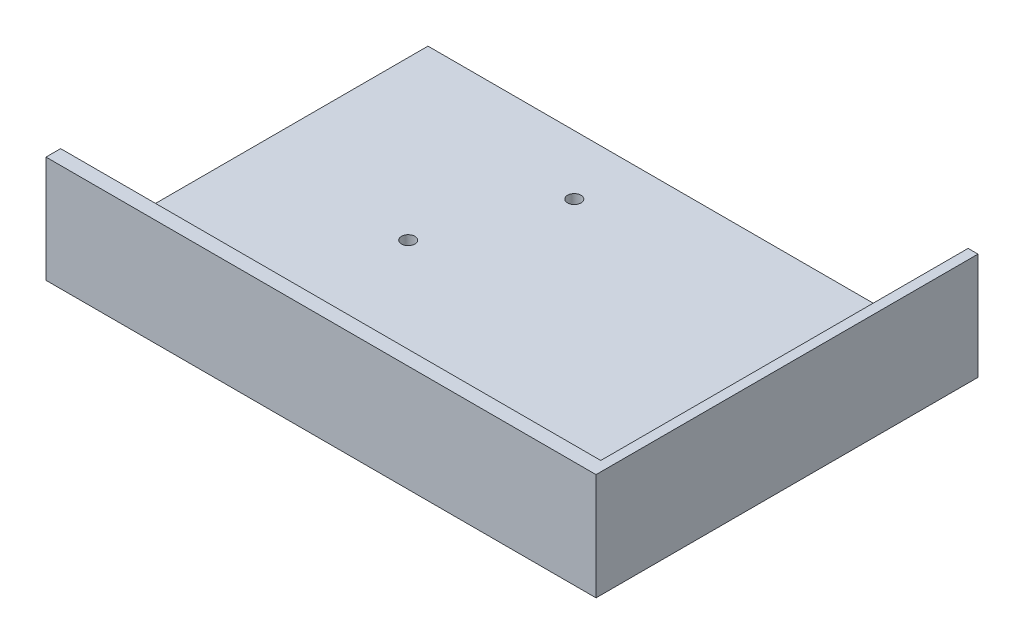
SolidWorks part; units mm, degrees
ref_plane "Front Plane" through (0, 0, 0) normal (0, 0, 1) x (1, 0, 0)
ref_plane "Top Plane" through (0, 0, 0) normal (0, 1, 0) x (1, 0, 0)
ref_plane "Right Plane" through (0, 0, 0) normal (1, 0, 0) x (0, 0, -1)
sketch "Sketch1" plane through (0, 0, 0) normal (0, 1, 0) x (1, 0, 0)
  line L1 (-139.1, -96.6) -> (139.1, -96.6)
  line L2 (-139.1, -96.6) -> (-139.1, 96.6)
  line L3 (-139.1, 96.6) -> (139.1, 96.6)
  line L4 (139.1, -96.6) -> (139.1, 96.6)
  line L5 (-139.1, -96.6) -> (139.1, 96.6) construction
  line L6 (-139.1, 96.6) -> (139.1, -96.6) construction
  dimension "D1" = 278.2
  dimension "D2" = 193.2
extrude "Shell Block" add sketch "Sketch1" along normal blind 27
ref_plane "Shell Front" through (0, 27, 0) normal (0, 1, 0) x (1, 0, 0)
sketch "Sketch2" plane through (0, 27, 0) normal (0, 1, 0) x (1, 0, 0)
  line L1 (-136.6, -92.9) -> (136.6, -92.9)
  line L2 (-136.6, -92.9) -> (-136.6, 92.9)
  line L3 (-136.6, 92.9) -> (136.6, 92.9)
  line L4 (136.6, -92.9) -> (136.6, 92.9)
  line L5 (-136.6, -92.9) -> (136.6, 92.9) construction
  line L6 (-136.6, 92.9) -> (136.6, -92.9) construction
  dimension "D1" = 273.2
  dimension "D2" = 185.8
extrude "Front Opening" cut sketch "Sketch2" against normal blind 1.5
ref_plane "Under Lip" through (0, 25.5, 0) normal (0, 1, 0) x (1, 0, 0)
sketch "Sketch3" plane through (0, 25.5, 0) normal (0, 1, 0) x (1, 0, 0)
  line L1 (-136.6, -94.1) -> (136.6, -94.1)
  line L2 (-136.6, -94.1) -> (-136.6, 94.1)
  line L3 (-136.6, 94.1) -> (136.6, 94.1)
  line L4 (136.6, -94.1) -> (136.6, 94.1)
  line L5 (-136.6, -94.1) -> (136.6, 94.1) construction
  line L6 (-136.6, 94.1) -> (136.6, -94.1) construction
  dimension "D1" = 273.2
  dimension "D2" = 188.2
extrude "Display Pocket" cut sketch "Sketch3" against normal blind 22.5
ref_plane "Back Inner" through (0, 3, 0) normal (0, 1, 0) x (1, 0, 0)
sketch "Sketch4" plane through (0, 3, 0) normal (0, 1, 0) x (1, 0, 0)
  line L1 (-69, 28) -> (-66, 28)
  line L2 (-69, 28) -> (-69, 84)
  line L3 (-69, 84) -> (-66, 84)
  line L4 (-66, 28) -> (-66, 84)
  line L6 (-69, -84) -> (-66, -84)
  line L7 (-69, -84) -> (-69, -28)
  line L8 (-69, -28) -> (-66, -28)
  line L9 (-66, -84) -> (-66, -28)
  line L11 (-77, 28) -> (-74, 28)
  line L12 (-77, 28) -> (-77, 84)
  line L13 (-77, 84) -> (-74, 84)
  line L14 (-74, 28) -> (-74, 84)
  line L16 (-77, -84) -> (-74, -84)
  line L17 (-77, -84) -> (-77, -28)
  line L18 (-77, -28) -> (-74, -28)
  line L19 (-74, -84) -> (-74, -28)
  line L21 (-85, 28) -> (-82, 28)
  line L22 (-85, 28) -> (-85, 84)
  line L23 (-85, 84) -> (-82, 84)
  line L24 (-82, 28) -> (-82, 84)
  line L26 (-85, -84) -> (-82, -84)
  line L27 (-85, -84) -> (-85, -28)
  line L28 (-85, -28) -> (-82, -28)
  line L29 (-82, -84) -> (-82, -28)
  line L31 (-93, 28) -> (-90, 28)
  line L32 (-93, 28) -> (-93, 84)
  line L33 (-93, 84) -> (-90, 84)
  line L34 (-90, 28) -> (-90, 84)
  line L36 (-93, -84) -> (-90, -84)
  line L37 (-93, -84) -> (-93, -28)
  line L38 (-93, -28) -> (-90, -28)
  line L39 (-90, -84) -> (-90, -28)
  line L41 (-101, 28) -> (-98, 28)
  line L42 (-101, 28) -> (-101, 84)
  line L43 (-101, 84) -> (-98, 84)
  line L44 (-98, 28) -> (-98, 84)
  line L46 (-101, -84) -> (-98, -84)
  line L47 (-101, -84) -> (-101, -28)
  line L48 (-101, -28) -> (-98, -28)
  line L49 (-98, -84) -> (-98, -28)
  line L51 (-109, 28) -> (-106, 28)
  line L52 (-109, 28) -> (-109, 84)
  line L53 (-109, 84) -> (-106, 84)
  line L54 (-106, 28) -> (-106, 84)
  line L56 (-109, -84) -> (-106, -84)
  line L57 (-109, -84) -> (-109, -28)
  line L58 (-109, -28) -> (-106, -28)
  line L59 (-106, -84) -> (-106, -28)
  line L61 (-117, 28) -> (-114, 28)
  line L62 (-117, 28) -> (-117, 84)
  line L63 (-117, 84) -> (-114, 84)
  line L64 (-114, 28) -> (-114, 84)
  line L66 (-117, -84) -> (-114, -84)
  line L67 (-117, -84) -> (-117, -28)
  line L68 (-117, -28) -> (-114, -28)
  line L69 (-114, -84) -> (-114, -28)
  line L71 (-125, 28) -> (-122, 28)
  line L72 (-125, 28) -> (-125, 84)
  line L73 (-125, 84) -> (-122, 84)
  line L74 (-122, 28) -> (-122, 84)
  line L76 (-125, -84) -> (-122, -84)
  line L77 (-125, -84) -> (-125, -28)
  line L78 (-125, -28) -> (-122, -28)
  line L79 (-122, -84) -> (-122, -28)
extrude "Vent Slots" cut sketch "Sketch4" against normal blind 4
sketch "Sketch5" plane through (0, 0, 0) normal (1, 0, 0) x (0, 0, -1)
  line L1 (-29, 5) -> (29, 5)
  line L2 (-29, 5) -> (-29, 21)
  line L3 (-29, 21) -> (29, 21)
  line L4 (29, 5) -> (29, 21)
extrude "Cable Exit (-X short side)" cut sketch "Sketch5" against normal blind 140.1
sketch "Sketch6" plane through (0, 3, 0) normal (0, 1, 0) x (1, 0, 0)
  circle A0 centre (-40, -45) radius 1.7
  circle A1 centre (-40, 45) radius 1.7
  circle A2 centre (40, -45) radius 1.7
  circle A3 centre (40, 45) radius 1.7
  circle A4 centre (-52, -15) radius 1.7
  circle A5 centre (-52, 15) radius 1.7
  circle A6 centre (52, -15) radius 1.7
  circle A7 centre (52, 15) radius 1.7
  circle A8 centre (-12, -82) radius 1.7
  circle A9 centre (-12, 82) radius 1.7
  circle A10 centre (12, -82) radius 1.7
  circle A11 centre (12, 82) radius 1.7
  circle A12 centre (-124, -12) radius 1.7
  circle A13 centre (-124, 12) radius 1.7
  circle A14 centre (124, -12) radius 1.7
  circle A15 centre (124, 12) radius 1.7
  circle A16 centre (-72, 12) radius 1.7
  circle A17 centre (-72, -12) radius 1.7
extrude "Bolt Holes" cut sketch "Sketch6" against normal blind 4
sketch "Sketch7" plane through (0, 0, 0) normal (0, 1, 0) x (1, 0, 0)
  line L1 (-200, -200) -> (0, -200)
  line L2 (-200, -200) -> (-200, 200)
  line L3 (-200, 200) -> (0, 200)
  line L4 (0, -200) -> (0, 200)
extrude "Keep one half (X)" cut sketch "Sketch7" against normal through all and the other way through all
sketch "Sketch8" plane through (0, 0, 0) normal (0, 1, 0) x (1, 0, 0)
  line L1 (-200, 0) -> (200, 0)
  line L2 (-200, 0) -> (-200, 200)
  line L3 (-200, 200) -> (200, 200)
  line L4 (200, 0) -> (200, 200)
extrude "Keep one quarter (Z)" cut sketch "Sketch8" against normal through all and the other way through all
equation "\"DispL\"= 272.0"
equation "\"DispW\"= 187.0"
equation "\"DispT\"= 20.0"
equation "\"Clr\"= 0.6"
equation "\"Wall\"= 2.5"
equation "\"BackT\"= 3.0"
equation "\"CableRoom\"= 4.0"
equation "\"LipW\"= 1.2"
equation "\"LipT\"= 1.5"
equation "\"CableW\"= 58.0"
equation "\"CableH\"= 16.0"
equation "\"BoltD\"= 3.4"
equation "\"ShellL\"= \"DispL\" + 2 * \"Clr\" + 2 * \"Wall\""
equation "\"ShellW\"= \"DispW\" + 2 * \"Clr\" + 2 * \"Wall\""
equation "\"ShellH\"= \"BackT\" + \"DispT\" + \"CableRoom\""
equation "\"D1@Sketch1\" = \"ShellL\""
equation "\"D2@Sketch1\" = \"ShellW\""
equation "\"D1@Shell Block\" = \"ShellH\""
equation "\"D1@Shell Front\" = \"ShellH\""
equation "\"D1@Sketch2\" = \"DispL\" + 2 * \"Clr\""
equation "\"D2@Sketch2\" = \"DispW\" + 2 * \"Clr\" - 2 * \"LipW\""
equation "\"D1@Front Opening\" = \"LipT\""
equation "\"D1@Under Lip\" = \"ShellH\" - \"LipT\""
equation "\"D1@Sketch3\" = \"DispL\" + 2 * \"Clr\""
equation "\"D2@Sketch3\" = \"DispW\" + 2 * \"Clr\""
equation "\"D1@Display Pocket\" = \"ShellH\" - \"LipT\" - \"BackT\""
equation "\"D1@Back Inner\" = \"BackT\""
